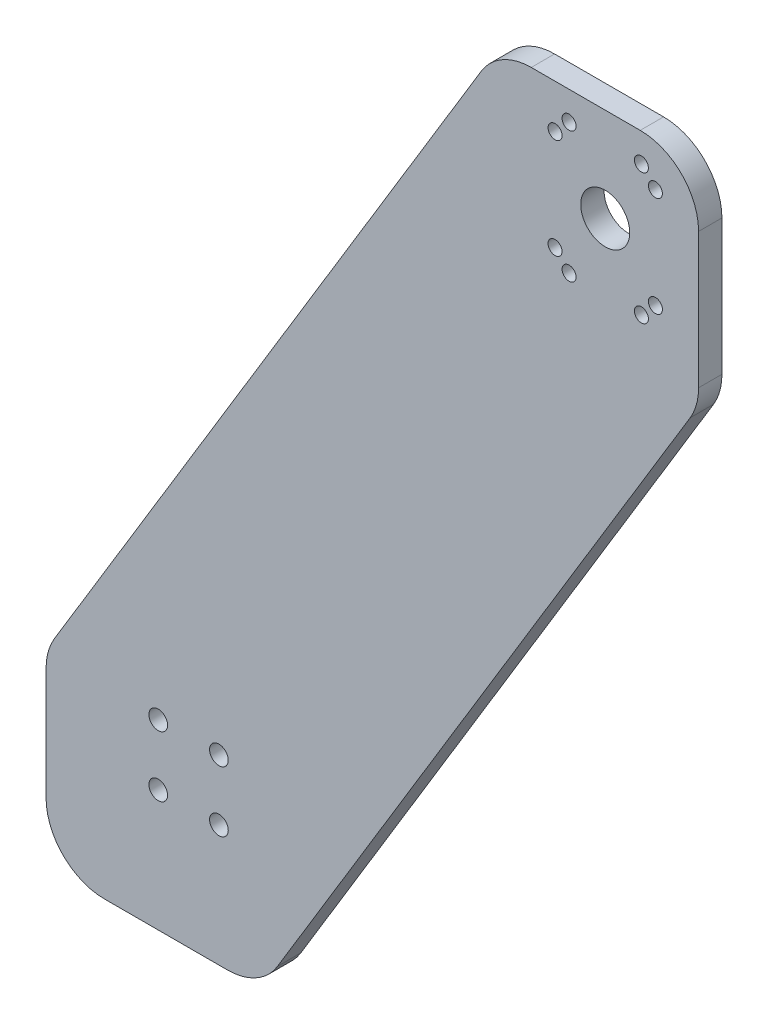
SolidWorks part; units mm, degrees
ref_plane "Piano frontale" through (0, 0, 0) normal (0, 0, 1) x (1, 0, 0)
ref_plane "Piano superiore" through (0, 0, 0) normal (0, 1, 0) x (1, 0, 0)
ref_plane "Piano destro" through (0, 0, 0) normal (1, 0, 0) x (0, 0, -1)
sketch "Schizzo1" plane through (0, 0, 0) normal (0, 0, 1) x (1, 0, 0)
  line L0 (25, 0) -> (77.7546, 0)
  line L1 (99.1387, 12.0493) -> (275.9682, 304.0295)
  line L2 (279.5841, 316.9801) -> (279.5841, 375)
  line L3 (254.5841, 400) -> (207.8857, 400)
  line L4 (0, 73.0199) -> (0, 25)
  line L5 (186.5016, 387.9507) -> (3.6159, 85.9705)
  line L6 (261.6765, 396.2552) -> (-22.3051, -72.6542) construction
  line L7 (20.2808, 65) -> (116.5802, 65) construction
  line L8 (61.0612, 65) -> (61.0612, 110.084) construction
  line L9 (239.5841, 359.7762) -> (211.0935, 388.2668) construction
  line L10 (239.5841, 359.7762) -> (201.235, 359.7762) construction
  line L11 (239.5841, 359.7762) -> (239.5841, 402.6918) construction
  line L13 (255.0841, 331.7762) -> (224.0841, 331.7762) construction
  line L14 (255.0841, 331.7762) -> (255.0841, 387.7762) construction
  line L15 (255.0841, 387.7762) -> (224.0841, 387.7762) construction
  line L16 (224.0841, 331.7762) -> (224.0841, 387.7762) construction
  line L17 (255.0841, 331.7762) -> (224.0841, 387.7762) construction
  line L18 (255.0841, 387.7762) -> (224.0841, 331.7762) construction
  circle A0 centre (48.0612, 78) radius 4
  circle A1 centre (74.0612, 78) radius 4
  circle A2 centre (74.0612, 52) radius 4
  circle A3 centre (48.0612, 52) radius 4
  circle A4 centre (239.5841, 359.7762) radius 10.5
  circle A5 centre (239.5841, 359.7762) radius 30.41 construction
  arc A6 (99.1387, 12.0493) -> (77.7546, 0) centre (77.7546, 25) cw
  arc A7 (25, 0) -> (0, 25) centre (25, 25) cw
  arc A8 (0, 73.0199) -> (3.6159, 85.9705) centre (25, 73.0199) cw
  arc A9 (279.5841, 316.9801) -> (275.9682, 304.0295) centre (254.5841, 316.9801) cw
  arc A10 (279.5841, 375) -> (254.5841, 400) centre (254.5841, 375) ccw
  arc A11 (207.8857, 400) -> (186.5016, 387.9507) centre (207.8857, 375) ccw
  circle A12 centre (224.0841, 387.7762) radius 3
  circle A13 centre (255.0841, 387.7762) radius 3
  circle A14 centre (261.0872, 381.2793) radius 3
  circle A15 centre (261.0872, 338.2731) radius 3
  circle A16 centre (255.0841, 331.7762) radius 3
  circle A17 centre (224.0841, 331.7762) radius 3
  circle A18 centre (218.0809, 338.2731) radius 3
  circle A19 centre (218.0809, 381.2793) radius 3
  point P27 (218.0809, 381.2793)
  point P28 (261.0872, 381.2793)
  point P29 (261.0872, 338.2731)
  point P30 (218.0809, 338.2731)
  point P39 (0, 0)
  point P42 (0, 80)
  point P45 (279.5841, 310)
  point P48 (279.5841, 400)
  dimension "D6" = 8
  dimension "D7" = 13
  dimension "D9" = 21
  dimension "D11" = 45
  dimension "D14" = 25
  dimension "D15" = 6
  dimension "D16" = 65
  dimension "D17" = 60.82
  dimension "D1" = 121.2
  dimension "D2" = 120
  dimension "D3" = 80
  dimension "D4" = 400
  dimension "D5" = 90
  dimension "D8" = 13
  dimension "D10" = 40
  dimension "D12" = 31
  dimension "D13" = 56
extrude "Estrusione-Estrusione2" add sketch "Schizzo1" against normal blind 10
sketch "Schizzo2" plane through (0, 0, 0) normal (0, -1, 0) x (1, 0, 0)
  line L0 (25, -5) -> (77.7546, -5) construction
  line L1 (25, -10) -> (25, 0) construction
  line L2 (77.7546, -10) -> (77.7546, 0) construction
  line L3 (51.3773, -5) -> (51.3773, 0) construction
  line L4 (25, 0) -> (77.7546, 0) construction
  circle A0 centre (51.3773, -5) radius 2
  circle A1 centre (78.8773, -5) radius 2
  circle A2 centre (23.8773, -5) radius 2
  dimension "D1" = 4
  dimension "D2" = 27.5
extrude "Taglio-Estrusione1" cut sketch "Schizzo2" against normal blind 15
